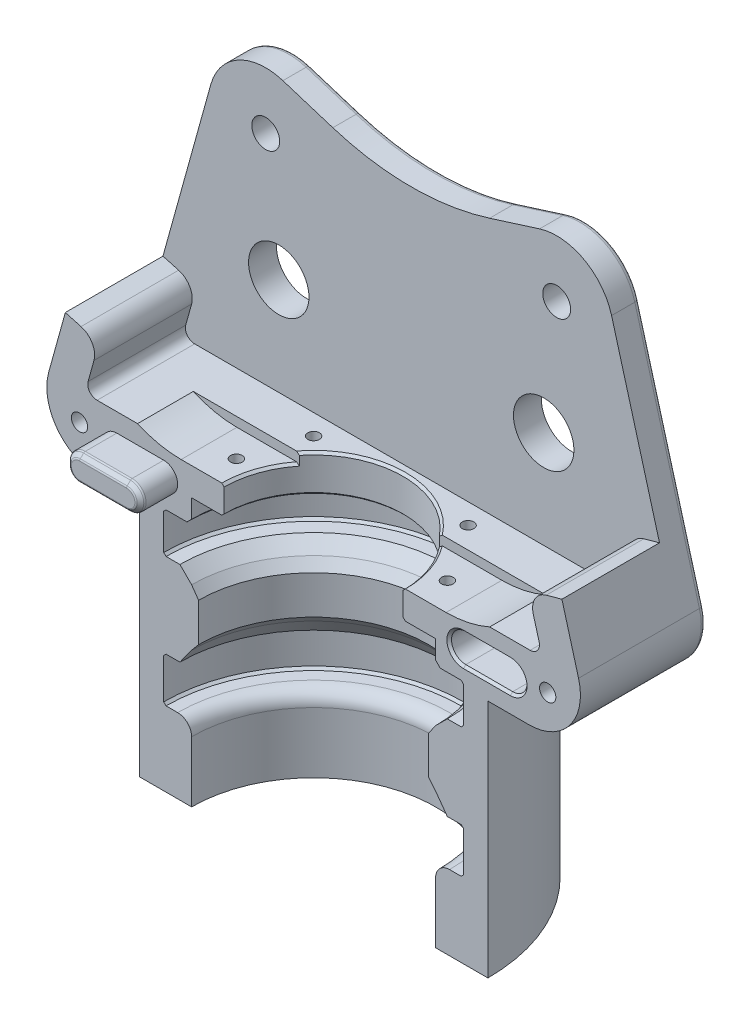
SolidWorks part; units mm, degrees
material "ABS PC"
ref_plane "前视基准面" through (0, 0, 0) normal (0, 0, 1) x (1, 0, 0)
ref_plane "上视基准面" through (0, 0, 0) normal (0, 1, 0) x (1, 0, 0)
ref_plane "右视基准面" through (0, 0, 0) normal (1, 0, 0) x (0, 0, -1)
sketch "草图1" plane through (0, 0, 0) normal (0, 1, 0) x (1, 0, 0)
  circle A0 centre (0, 0) radius 40
  dimension "D1" = 80
extrude "凸台-拉伸1" add sketch "草图1" along normal blind 80
sketch "草图3" plane through (0, 0, 0) normal (0, -1, 0) x (1, 0, 0)
  circle A0 centre (0, 0) radius 37.5
  circle A1 centre (0, 0) radius 40
  dimension "D1" = 75
  dimension "D2" = 80
extrude "切除-拉伸2" cut sketch "草图3" against normal offset from surface (66 mm away) 14 up to face at (0, 80, 40)
sketch "草图4" plane through (0, 0, 0) normal (0, -1, 0) x (1, 0, 0)
  circle A0 centre (0, 0) radius 26.25
  dimension "D1" = 52.5
extrude "切除-拉伸3" cut sketch "草图4" against normal blind 60
sketch "草图5" plane through (0, 80, 0) normal (0, 1, 0) x (1, 0, 0)
  circle A0 centre (0, 0) radius 19.25
  dimension "D1" = 38.5
extrude "切除-拉伸4" cut sketch "草图5" against normal through all both and the other way through all
sketch "草图7" plane through (0, 0, 0) normal (1, 0, 0) x (0, 0, -1)
  line L0 (19.25, 87) -> (19.25, 80)
  line L1 (19.25, 80) -> (-19.25, 80) construction
  line L2 (19.25, 80) -> (40, 80)
  line L4 (19.25, 87) -> (33, 87)
  line L5 (0, 0) -> (0, 120.3572) construction
  line L6 (40, 66) -> (40, 80) construction
  arc A0 (40, 80) -> (33, 87) centre (33, 80) ccw
  dimension "D1" = 7
revolve "旋转1" add sketch "草图7" angle 360 about L5
sketch "草图2" plane through (0, 87, 0) normal (0, 1, 0) x (1, 0, 0)
  line L0 (0, 0) -> (-6.0822, 22.6993) construction
  line L1 (-6.0822, 22.6993) -> (6.0822, 22.6993) construction
  line L2 (0, 22.6993) -> (0, 0) construction
  circle A0 centre (0, 0) radius 23.5 construction
  circle A1 centre (-6.0822, 22.6993) radius 1.25
  circle A2 centre (6.0822, 22.6993) radius 1.25
  circle A3 centre (16.617, 16.617) radius 1.25
  circle A4 centre (22.6993, 6.0822) radius 1.25
  circle A5 centre (22.6993, -6.0822) radius 1.25
  circle A6 centre (16.617, -16.617) radius 1.25
  circle A7 centre (6.0822, -22.6993) radius 1.25
  circle A8 centre (-6.0822, -22.6993) radius 1.25
  circle A9 centre (-16.617, -16.617) radius 1.25
  circle A10 centre (-22.6993, -6.0822) radius 1.25
  circle A11 centre (-22.6993, 6.0822) radius 1.25
  circle A12 centre (-16.617, 16.617) radius 1.25
  point P5 (0, 22.6993)
  point P29 (0, 0)
  dimension "D1" = 47
  dimension "D2" = 2.5
  dimension "D3" = 12
extrude "切除-拉伸1" cut sketch "草图2" against normal through all both and the other way through all
ref_plane "基准面1" through (0, 80, 0) normal (0, -1, 0) x (-1, 0, 0)
sketch "草图6" plane through (0, 80, 0) normal (0, -1, 0) x (-1, 0, 0)
  line L1 (-57, 27) -> (57, 27)
  line L2 (-57, 27) -> (-57, -27)
  line L3 (-57, -27) -> (57, -27)
  line L4 (57, 27) -> (57, -27)
  line L5 (-57, 27) -> (57, -27) construction
  line L6 (-57, -27) -> (57, 27) construction
  point P0 (0, 0)
  dimension "D1" = 54
  dimension "D2" = 114
extrude "凸台-拉伸2" add sketch "草图6" along normal blind 14
sketch "草图8" plane through (0, 0, -27) normal (0, 0, -1) x (-1, 0, 0)
  line L0 (-57, 80) -> (-43.1048, 130.1226)
  line L1 (-29.5127, 66) -> (-57, 66) construction
  line L2 (0, 0) -> (0, 122.5955) construction
  line L3 (-27.6131, 138.532) -> (-16.8656, 135.14)
  line L5 (-55, 80) -> (55, 80) construction
  line L6 (0, 132.5417) -> (-11.4514, 132.5417) construction
  line L7 (57, 80) -> (43.1048, 130.1226)
  line L8 (27.6131, 138.532) -> (16.8656, 135.14)
  line L9 (-57, 80) -> (57, 80)
  circle A0 centre (-28.5, 101) radius 6.5
  circle A1 centre (-28.5, 101) radius 3 construction
  circle A2 centre (-31.3, 126.85) radius 3
  arc A3 (-43.1048, 130.1226) -> (-27.6131, 138.532) centre (-31.3, 126.85) cw
  arc A6 (-16.8656, 135.14) -> (16.8656, 135.14) centre (0, 188.5783) ccw
  arc A7 (43.1048, 130.1226) -> (27.6131, 138.532) centre (31.3, 126.85) ccw
  circle A8 centre (31.3, 126.85) radius 3
  circle A9 centre (28.5, 101) radius 3 construction
  circle A10 centre (28.5, 101) radius 6.5
  dimension "D3" = 13
  dimension "D4" = 6
  dimension "D8" = 6
  dimension "D9" = 12.25
  dimension "D11" = 11.4514
  dimension "D1" = 35
  dimension "D2" = 28.5
  dimension "D5" = 55.14
  dimension "D6" = 25.85
  dimension "D7" = 2.8
  dimension "D10" = 11.27
extrude "凸台-拉伸3" add sketch "草图8" against normal blind 6
sketch "草图9" plane through (0, 0, -27) normal (0, 0, -1) x (-1, 0, 0)
  line L0 (-29.5127, 66) -> (-57, 66) construction
  line L1 (-43.1048, 130.1226) -> (-57, 80) construction
  line L2 (-57, 80) -> (-46.3531, 80)
  line L3 (-55, 80) -> (55, 80) construction
  line L4 (-46.3531, 80) -> (-46.3531, 66)
  line L5 (57, 66) -> (29.5127, 66) construction
  line L6 (57, 80) -> (43.1048, 130.1226) construction
  line L7 (57, 80) -> (46.3531, 80)
  line L8 (46.3531, 80) -> (46.3531, 66)
  arc A0 (-57, 80) -> (-46.3531, 66) centre (-46.3531, 77.0484) ccw
  arc A1 (57, 80) -> (46.3531, 66) centre (46.3531, 77.0484) cw
extrude "凸台-拉伸4" add sketch "草图9" against normal up to surface (54 mm away) up to face at (43.2564, 73, 27)
sketch "草图10" plane through (0, 0, -27) normal (0, 0, -1) x (-1, 0, 0)
  line L0 (-57, 80) -> (-60.8811, 66)
  line L1 (-60.8811, 66) -> (-46.3531, 66)
  line L2 (-29.5127, 66) -> (-57, 66) construction
  line L3 (-43.1048, 130.1226) -> (-57, 80) construction
  line L4 (0, 0) -> (0, 34.6833) construction
  line L5 (57, 80) -> (60.8811, 66)
  line L6 (60.8811, 66) -> (46.3531, 66)
  arc A0 (-57, 80) -> (-46.3531, 66) centre (-46.3531, 77.0484) ccw
  arc A1 (57, 80) -> (46.3531, 66) centre (46.3531, 77.0484) cw
extrude "切除-拉伸5" cut sketch "草图10" against normal through all both and the other way through all
sketch "草图11" plane through (0, 0, 27) normal (0, 0, 1) x (1, 0, 0)
  line L0 (-57, 80) -> (-43.1048, 130.1226) construction
  line L1 (-27.6131, 138.532) -> (-16.8656, 135.14) construction
  line L2 (16.8656, 135.14) -> (27.6131, 138.532) construction
  line L3 (43.1048, 130.1226) -> (57, 80) construction
  line L4 (-57, 80) -> (-43.1048, 130.1226)
  line L5 (-27.6131, 138.532) -> (-16.8656, 135.14)
  line L6 (16.8656, 135.14) -> (27.6131, 138.532)
  line L7 (43.1048, 130.1226) -> (57, 80)
  line L8 (-46.3531, 66) -> (46.3531, 66)
  arc A0 (-57, 80) -> (-46.3531, 66) centre (-46.3531, 77.0484) ccw construction
  circle A1 centre (28.5, 101) radius 6.5
  circle A2 centre (28.5, 101) radius 6.5
  circle A3 centre (31.3, 126.85) radius 3
  circle A4 centre (31.3, 126.85) radius 3
  circle A5 centre (-31.3, 126.85) radius 3
  circle A6 centre (-31.3, 126.85) radius 3
  circle A7 centre (-28.5, 101) radius 6.5
  circle A8 centre (-28.5, 101) radius 6.5
  arc A9 (-27.6131, 138.532) -> (-43.1048, 130.1226) centre (-31.3, 126.85) ccw construction
  arc A10 (43.1048, 130.1226) -> (27.6131, 138.532) centre (31.3, 126.85) ccw construction
  arc A11 (46.3531, 66) -> (57, 80) centre (46.3531, 77.0484) ccw construction
  arc A12 (-57, 80) -> (-46.3531, 66) centre (-46.3531, 77.0484) ccw
  arc A13 (-27.6131, 138.532) -> (-43.1048, 130.1226) centre (-31.3, 126.85) ccw
  arc A14 (43.1048, 130.1226) -> (27.6131, 138.532) centre (31.3, 126.85) ccw
  arc A15 (46.3531, 66) -> (57, 80) centre (46.3531, 77.0484) ccw
  arc A16 (-16.8656, 135.14) -> (16.8656, 135.14) centre (0, 188.5783) ccw construction
  arc A17 (-16.8656, 135.14) -> (16.8656, 135.14) centre (0, 188.5783) ccw
  dimension "D1" = 0
  dimension "D2" = 0
  dimension "D3" = 0
  dimension "D4" = 0
extrude "凸台-拉伸5" add sketch "草图11" against normal blind 6
fillet "圆角2" radius 3 5 edges at (-29.5127, 73, -27) (29.5127, 73, -27) (0, 87, -27) (-26.4189, 85.1185, -27) (28.4635, 83.1873, -27)
fillet "圆角3" radius 3 5 edges at (29.5127, 73, 27) (-29.5127, 73, 27) (0, 87, 27) (26.4189, 85.1185, 27) (-28.4635, 83.1873, 27)
fillet "圆角4" radius 1 28 edges at (-50.0524, 105.0613, -27) (-37.1442, 137.6161, -27) (-22.2393, 136.836, -27) (0, 132.5417, -27) (22.2393, 136.836, -27) (37.1442, 137.6161, -27) (50.0524, 105.0613, -27) (55.1474, 70.3605, -27) (55.1474, 70.3605, 27) (-55.1474, 70.3605, -27) (-55.1474, 70.3605, 27) (-38.5795, 66, -27) (38.5795, 66, 27) (50.0524, 105.0613, 27) (37.1442, 137.6161, 27) (22.2393, 136.836, 27) (0, 132.5417, 27) (-22.2393, 136.836, 27) (-37.1442, 137.6161, 27) (-50.0524, 105.0613, 27) (38.5795, 66, -27) (0, 66, -40) (29.6395, 66, -27.236) (-29.6395, 66, -27.236) (-38.5795, 66, 27) (0, 66, 40) (-29.6395, 66, 27.236) (29.6395, 66, 27.236)
sketch "草图12" plane through (0, 87, 0) normal (0, 1, 0) x (1, 0, 0)
  line L1 (-57, 21) -> (57, 21)
  line L2 (-57, 21) -> (-57, -21)
  line L3 (-57, -21) -> (57, -21)
  line L4 (57, 21) -> (57, -21)
  line L5 (-57, 21) -> (57, -21) construction
  line L6 (-57, -21) -> (57, 21) construction
  point P0 (0, 0)
extrude "切除-拉伸6" cut sketch "草图12" against normal up to surface (7 mm away) up to face at (47.011, 80, 0)
sketch "草图13" plane through (0, 66, 0) normal (0, -1, 0) x (1, 0, 0)
  circle A0 centre (-16.617, 16.617) radius 1.25 construction
  circle A1 centre (-22.6993, 6.0822) radius 1.25 construction
  circle A2 centre (-22.6993, -6.0822) radius 1.25 construction
  circle A3 centre (-16.617, -16.617) radius 1.25 construction
  circle A6 centre (16.617, -16.617) radius 1.25 construction
  circle A7 centre (22.6993, -6.0822) radius 1.25 construction
  circle A8 centre (22.6993, 6.0822) radius 1.25 construction
  circle A9 centre (16.617, 16.617) radius 1.25 construction
  circle A12 centre (0, 0) radius 19.25 construction
  circle A13 centre (-16.617, 16.617) radius 1.25
  circle A14 centre (-22.6993, 6.0822) radius 1.25
  circle A15 centre (-22.6993, -6.0822) radius 1.25
  circle A16 centre (-16.617, -16.617) radius 1.25
  circle A19 centre (16.617, -16.617) radius 1.25
  circle A20 centre (22.6993, -6.0822) radius 1.25
  circle A21 centre (22.6993, 6.0822) radius 1.25
  circle A22 centre (16.617, 16.617) radius 1.25
  circle A25 centre (0, 0) radius 19.25
extrude "切除-拉伸7" cut sketch "草图13" against normal through all both and the other way through all
sketch "草图14" plane through (0, 0, 0) normal (0, 0, 1) x (1, 0, 0)
  line L1 (-78.6939, -162.3471) -> (78.6939, -162.3471)
  line L2 (-78.6939, -162.3471) -> (-78.6939, 162.3471)
  line L3 (-78.6939, 162.3471) -> (78.6939, 162.3471)
  line L4 (78.6939, -162.3471) -> (78.6939, 162.3471)
  line L5 (-78.6939, -162.3471) -> (78.6939, 162.3471) construction
  line L6 (-78.6939, 162.3471) -> (78.6939, -162.3471) construction
extrude "切除-拉伸8" cut sketch "草图14" along normal through all
chamfer "倒角2" distance 0.5 angle 45 1 edges at (0, 80, -19.25)
sketch "草图15" plane through (0, 0, 0) normal (0, 0, 1) x (1, 0, 0)
  line L2 (0, 0) -> (0, 101) construction
  line L3 (-26.25, 0) -> (26.25, 0) construction
  line L4 (-28.5, 101) -> (28.5, 101) construction
  line L5 (-28.5, 124) -> (28.5, 124)
  line L6 (-28.5, 78) -> (28.5, 78)
  circle A4 centre (28.5, 101) radius 23 construction
  arc A5 (-28.5, 124) -> (-28.5, 78) centre (-28.5, 101) ccw
  arc A6 (28.5, 78) -> (28.5, 124) centre (28.5, 101) ccw
  point P10 (0, 101)
  dimension "D1" = 46
extrude "切除-拉伸9" cut sketch "草图15" against normal blind 12
sketch "草图16" plane through (0, 60, 0) normal (0, -1, 0) x (1, 0, 0)
  line L2 (-19.25, 0) -> (-26.25, 0)
  line L3 (26.25, 0) -> (19.25, 0)
  line L4 (-19.25, 0) -> (-26.25, 0)
  line L5 (26.25, 0) -> (19.25, 0)
  circle A1 centre (-16.617, -16.617) radius 1.25
  circle A2 centre (-16.617, -16.617) radius 1.25
  circle A3 centre (-6.0822, -22.6993) radius 1.25
  circle A4 centre (-6.0822, -22.6993) radius 1.25 construction
  circle A5 centre (6.0822, -22.6993) radius 1.25
  circle A6 centre (6.0822, -22.6993) radius 1.25 construction
  circle A7 centre (16.617, -16.617) radius 1.25
  circle A8 centre (16.617, -16.617) radius 1.25
  circle A9 centre (22.6993, -6.0822) radius 1.25
  circle A10 centre (22.6993, -6.0822) radius 1.25
  circle A11 centre (-22.6993, -6.0822) radius 1.25
  circle A12 centre (-22.6993, -6.0822) radius 1.25
  arc A14 (-26.25, 0) -> (26.25, 0) centre (0, 0) ccw
  arc A15 (-19.25, 0) -> (19.25, 0) centre (0, 0) ccw
  arc A16 (-26.25, 0) -> (26.25, 0) centre (0, 0) ccw
  arc A17 (-19.25, 0) -> (19.25, 0) centre (0, 0) ccw
  dimension "D1" = 0
  dimension "D2" = 0
  dimension "D3" = 0
  dimension "D4" = 0
  dimension "D5" = 0
  dimension "D6" = 0
  dimension "D7" = 0
extrude "切除-拉伸10" cut sketch "草图16" against normal blind 12
chamfer "倒角1" distance 0.5 angle 45 1 edges at (0, 72, -19.25)
sketch "草图17" plane through (0, 0, 0) normal (0, 0, 1) x (1, 0, 0)
  line L0 (26.25, 55.8) -> (24.75, 53.6578)
  line L1 (26.25, 0) -> (26.25, 72) construction
  line L2 (24.75, 53.6578) -> (24.75, 45.3876)
  line L3 (24.75, 45.3876) -> (26.25, 43.6)
  line L4 (26.25, 55.8) -> (26.25, 43.6)
  line L5 (26.25, 72) -> (19.75, 72) construction
  line L6 (0, 0) -> (0, 20.5829) construction
  dimension "D1" = 35
  dimension "D2" = 40
  dimension "D3" = 1.5
  dimension "D4" = 16.2
  dimension "D5" = 12.2
revolve "旋转2" add sketch "草图17" angle 180 about L6
chamfer "倒角3" distance 0.5 angle 45 2 edges at (18.1702, 78, -6.3566) (-18.1702, 78, -6.3566)
sketch "草图18" plane through (0, 0, 0) normal (0, -1, 0) x (1, 0, 0)
  circle A0 centre (0, 0) radius 37.5
  arc A1 (-37.5, 0) -> (37.5, 0) centre (0, 0) ccw construction
extrude "切除-拉伸11" cut sketch "草图18" against normal blind 14.4 contours A0
sketch "草图19" plane through (0, 0, -21) normal (0, 0, 1) x (1, 0, 0)
  line L0 (-49.2171, 80) -> (-47.2553, 87.0768)
  line L1 (57, 80) -> (-57, 80) construction
  line L2 (-53.4141, 92.935) -> (-50.0413, 92)
  line L3 (-57, 80) -> (-43.1048, 130.1226) construction
  line L4 (-53.4141, 92.935) -> (-57, 80)
  line L5 (-57, 80) -> (-49.2171, 80)
  line L6 (0, 0) -> (0, 185.0256) construction
  line L7 (53.4141, 92.935) -> (57, 80)
  line L8 (53.4141, 92.935) -> (50.0413, 92)
  line L9 (49.2171, 80) -> (47.2553, 87.0768)
  line L10 (57, 80) -> (49.2171, 80)
  arc A0 (-50.0413, 92) -> (-47.2553, 87.0768) centre (-51.1099, 88.1454) cw
  arc A1 (50.0413, 92) -> (47.2553, 87.0768) centre (51.1099, 88.1454) ccw
  dimension "D3" = 4
  dimension "D1" = 7.5
  dimension "D2" = 12
extrude "凸台-拉伸6" add sketch "草图19" along normal up to surface (21 mm away) up to face at (-30.0506, 60.382, 0)
fillet "圆角5" radius 2 2 edges at (49.2171, 80, -10.5) (-49.2171, 80, -10.5)
sketch "草图20" plane through (0, 0, 0) normal (0, 0, 1) x (1, 0, 0)
  line L0 (-26.25, 67) -> (-32.25, 67)
  line L1 (-26.25, 72) -> (-26.25, 55.8) construction
  line L2 (-32.25, 67) -> (-32.25, 58.3151)
  line L4 (-26.25, 67) -> (-26.25, 55.8)
  line L5 (-26.25, 72) -> (26.25, 72) construction
  line L8 (-26.25, 55.8) -> (-28.7651, 58.3151)
  line L9 (-28.7651, 58.3151) -> (-32.25, 58.3151)
  line L10 (-26.25, 43.6) -> (-28.7651, 40.12)
  line L11 (-28.7651, 40.12) -> (-32.25, 40.12)
  line L12 (-32.25, 40.12) -> (-32.25, 30.478)
  line L13 (-32.25, 30.478) -> (-26.25, 30.478)
  line L14 (-26.25, 43.6) -> (-26.25, 14.4) construction
  line L15 (-26.25, 30.478) -> (-26.25, 43.6)
  line L16 (0, 0) -> (0, 32.3271) construction
  dimension "D1" = 6
  dimension "D2" = 5
revolve "切除-旋转1" cut sketch "草图20" angle 360 about L16
chamfer "倒角4" distance 1 angle 45 1 edges at (0, 67, -26.25)
chamfer "倒角5" distance 0.5 angle 45 4 edges at (0, 30.478, -32.25) (0, 40.12, -32.25) (0, 58.3151, -32.25) (0, 67, -32.25)
fillet "圆角6" radius 3 1 edges at (0, 30.478, -26.25)
sketch "草图21" plane through (0, 0, 0) normal (0, 0, 1) x (1, 0, 0)
  line L0 (-42.3371, 73) -> (-32.25, 73) construction
  line L1 (-42.3371, 76) -> (-32.25, 76)
  line L2 (-42.3371, 70) -> (-32.25, 70)
  line L3 (-37.5, 66) -> (-46.3531, 66) construction
  line L4 (-46.5873, 80) -> (-37.8808, 80) construction
  line L5 (-57, 80) -> (-53.4141, 92.935) construction
  line L6 (-26.25, 72) -> (-26.25, 68) construction
  line L7 (0, 0) -> (0, 37.4631) construction
  line L8 (42.3371, 73) -> (32.25, 73) construction
  line L9 (42.3371, 76) -> (32.25, 76)
  line L10 (42.3371, 70) -> (32.25, 70)
  arc A0 (-42.3371, 76) -> (-42.3371, 70) centre (-42.3371, 73) ccw
  arc A1 (-32.25, 70) -> (-32.25, 76) centre (-32.25, 73) ccw
  arc A2 (42.3371, 76) -> (42.3371, 70) centre (42.3371, 73) cw
  arc A3 (32.25, 70) -> (32.25, 76) centre (32.25, 73) cw
  point P2 (-37.2936, 73)
  point P21 (37.2936, 73)
  dimension "D1" = 4
  dimension "D2" = 4
  dimension "D3" = 16
  dimension "D4" = 6
extrude "凸台-拉伸7" add sketch "草图21" along normal blind 8 contours L2 A1 L1 A0
chamfer "倒角6" distance 1 angle 45 4 edges at (-37.2936, 76, 8) (-45.3371, 73, 8) (-29.25, 73, 8) (-37.2936, 70, 8)
fillet "圆角7" radius 0.5 8 edges at (-44.3371, 73, 8) (-37.2936, 75, 8) (-30.25, 73, 8) (-29.25, 73, 7) (-37.2936, 76, 7) (-45.3371, 73, 7) (-37.2936, 71, 8) (-37.2936, 70, 7)
sketch "草图22" plane through (0, 0, 0) normal (0, 0, 1) x (1, 0, 0)
  line L0 (42.3371, 76) -> (32.25, 76) construction
  line L1 (42.3371, 76) -> (32.25, 76) construction
  line L2 (42.3371, 70) -> (32.25, 70) construction
  line L3 (42.3371, 70) -> (32.25, 70) construction
  line L4 (42.3371, 76.08) -> (32.25, 76.08)
  line L5 (42.3371, 69.92) -> (32.25, 69.92)
  arc A0 (42.3371, 70) -> (42.3371, 76) centre (42.3371, 73) ccw construction
  arc A1 (32.25, 76) -> (32.25, 70) centre (32.25, 73) ccw construction
  arc A2 (42.3371, 70) -> (42.3371, 76) centre (42.3371, 73) ccw construction
  arc A3 (32.25, 76) -> (32.25, 70) centre (32.25, 73) ccw construction
  arc A4 (32.25, 76.08) -> (32.25, 69.92) centre (32.25, 73) ccw
  arc A5 (42.3371, 69.92) -> (42.3371, 76.08) centre (42.3371, 73) ccw
  dimension "D1" = 0.08
extrude "切除-拉伸12" cut sketch "草图22" against normal blind 8.2
chamfer "倒角7" distance 0.5 angle 45 4 edges at (37.2936, 69.92, 0) (45.4171, 73, 0) (29.17, 73, 0) (37.2936, 76.08, 0)
chamfer "倒角8" distance 1 angle 45 4 edges at (37.2936, 69.92, -8.2) (45.4171, 73, -8.2) (29.17, 73, -8.2) (37.2936, 76.08, -8.2)
sketch "草图24" plane through (0, 0, 0) normal (0, 0, 1) x (1, 0, 0)
  line L0 (-57, 80) -> (-53.4141, 92.935) construction
  line L1 (-37.5, 66) -> (-46.3531, 66) construction
  line L2 (0, 158.6177) -> (0, 142.4464) construction
  circle A0 centre (-50.3616, 74) radius 1.75
  circle A1 centre (-50.3616, 74) radius 3.5 construction
  circle A2 centre (50.3616, 74) radius 3.5 construction
  circle A3 centre (50.3616, 74) radius 1.75
  dimension "D3" = 3.5
  dimension "D4" = 7
  dimension "D1" = 8
  dimension "D2" = 8
extrude "切除-拉伸13" cut sketch "草图24" against normal blind 23
chamfer "倒角9" distance 1.6 angle 45 1 edges at (48.6116, 74, -23)
sketch "草图25" plane through (0, 0, -27) normal (0, 0, -1) x (-1, 0, 0)
  circle A0 centre (50.3616, 74) radius 1.75 construction
  circle A1 centre (50.3616, 74) radius 1.75 construction
  circle A2 centre (50.3616, 74) radius 3.65
  dimension "D1" = 7.3
extrude "切除-拉伸14" cut sketch "草图25" against normal blind 4
chamfer "倒角10" distance 0.5 angle 45 1 edges at (-54.0116, 74, -27)
